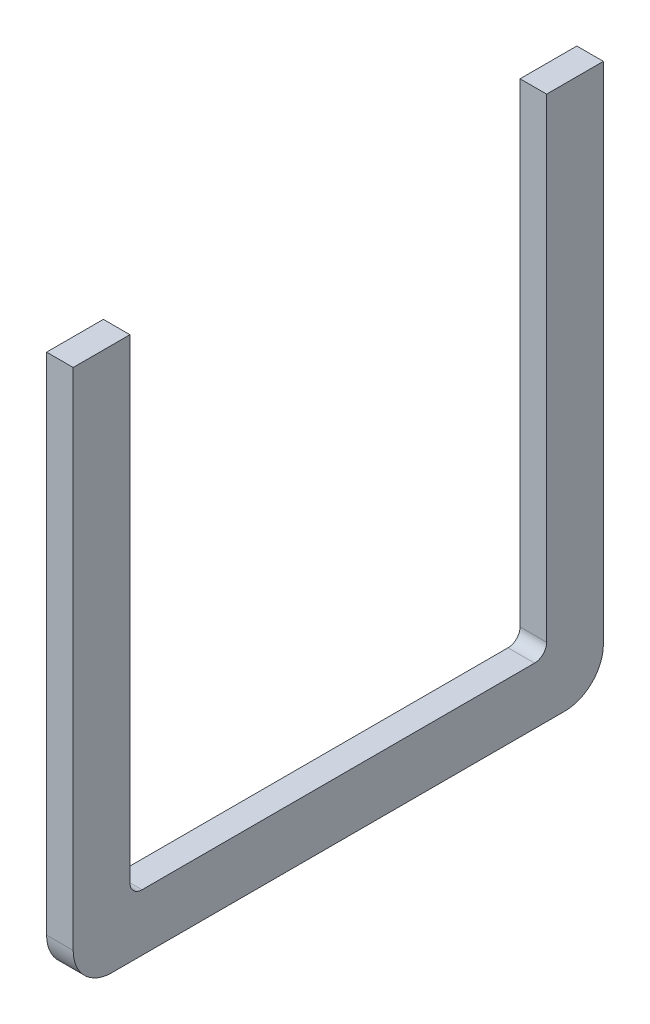
SolidWorks part; units mm, degrees
material "Acrylic (Medium-high impact)"
ref_plane "Front Plane" through (0, 0, 0) normal (0, 0, 1) x (1, 0, 0)
ref_plane "Top Plane" through (0, 0, 0) normal (0, 1, 0) x (1, 0, 0)
ref_plane "Right Plane" through (0, 0, 0) normal (1, 0, 0) x (0, 0, -1)
sketch "Sketch1" plane through (0, 0, 0) normal (1, 0, 0) x (0, 0, -1)
  line L0 (-47.625, 0) -> (47.625, 0)
  line L1 (55.753, 8.128) -> (55.753, 114.3)
  line L2 (55.753, 114.3) -> (50.165, 114.3)
  line L3 (50.165, 114.3) -> (50.165, 8.128)
  line L4 (47.625, 5.588) -> (-47.625, 5.588)
  line L5 (-50.165, 8.128) -> (-50.165, 114.3)
  line L6 (-50.165, 114.3) -> (-55.753, 114.3)
  line L7 (-55.753, 114.3) -> (-55.753, 8.128)
  arc A0 (-50.165, 8.128) -> (-47.625, 5.588) centre (-47.625, 8.128) ccw
  arc A1 (47.625, 5.588) -> (50.165, 8.128) centre (47.625, 8.128) ccw
  arc A2 (-55.753, 8.128) -> (-47.625, 0) centre (-47.625, 8.128) ccw
  arc A3 (47.625, 0) -> (55.753, 8.128) centre (47.625, 8.128) ccw
  point P12 (55.753, 0)
  dimension "D4" = 2.54
  dimension "D5" = 114.3
  dimension "D1" = 5.588
  dimension "D2" = 5.588
  dimension "D3" = 100.33
extrude "Boss-Extrude1" add sketch "Sketch1" along normal blind 5.588
sketch "Sketch2" plane through (5.588, 0, 0) normal (1, 0, 0) x (0, 0, -1)
  line L0 (-50.165, 114.3) -> (-43.815, 114.3)
  line L1 (-43.815, 114.3) -> (-43.815, 14.478)
  line L2 (-41.275, 11.938) -> (41.275, 11.938)
  line L3 (43.815, 14.478) -> (43.815, 114.3)
  line L4 (43.815, 114.3) -> (50.165, 114.3)
  line L5 (47.625, 5.588) -> (-47.625, 5.588) construction
  line L6 (-50.165, 8.128) -> (-50.165, 114.3) construction
  line L7 (50.165, 114.3) -> (50.165, 8.128) construction
  line L8 (-50.165, 8.128) -> (-50.165, 114.3)
  line L9 (47.625, 5.588) -> (-47.625, 5.588)
  line L10 (50.165, 114.3) -> (50.165, 8.128)
  arc A1 (-43.815, 14.478) -> (-41.275, 11.938) centre (-41.275, 14.478) ccw
  arc A2 (41.275, 11.938) -> (43.815, 14.478) centre (41.275, 14.478) ccw
  arc A3 (-50.165, 8.128) -> (-47.625, 5.588) centre (-47.625, 8.128) ccw construction
  arc A4 (47.625, 5.588) -> (50.165, 8.128) centre (47.625, 8.128) ccw construction
  arc A5 (-50.165, 8.128) -> (-47.625, 5.588) centre (-47.625, 8.128) ccw
  arc A6 (47.625, 5.588) -> (50.165, 8.128) centre (47.625, 8.128) ccw
  dimension "D3" = 2.54
  dimension "D1" = 6.35
  dimension "D2" = 6.35
extrude "Boss-Extrude2" add sketch "Sketch2" against normal up to surface (5.588 mm away)
